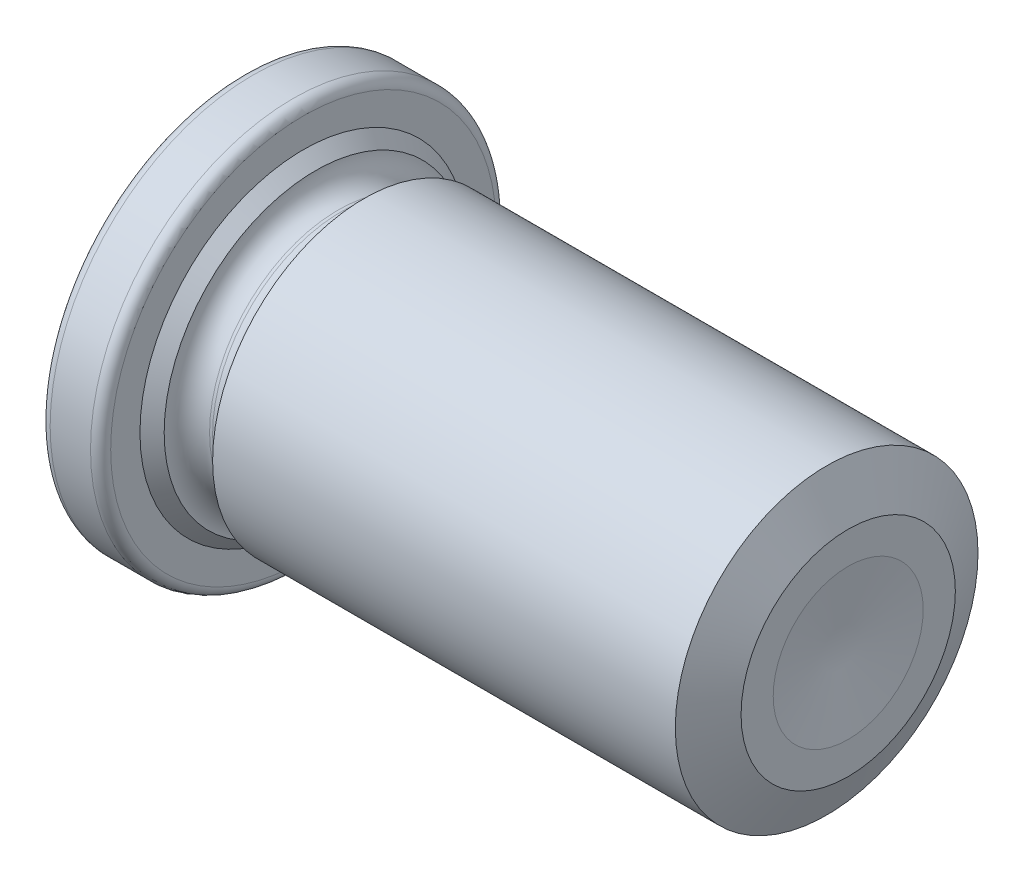
SolidWorks part; units mm, degrees
ref_plane "Front" through (0, 0, 0) normal (0, 0, 1) x (1, 0, 0)
ref_plane "Top" through (0, 0, 0) normal (0, 1, 0) x (1, 0, 0)
ref_plane "Right" through (0, 0, 0) normal (1, 0, 0) x (0, 0, -1)
sketch "Sketch1" plane through (0, 0, 0) normal (0, 0, 1) x (1, 0, 0)
  line L0 (-6.35, 0) -> (6.35, 0) construction
  line L1 (-6.35, 0) -> (-6.35, 4.2545)
  line L2 (-6.35, 4.2545) -> (-5.08, 4.2545)
  line L3 (-5.08, 4.2545) -> (-5.08, 3.429)
  line L4 (-5.08, 3.429) -> (-4.826, 3.175)
  line L5 (-4.826, 3.175) -> (-4.826, 2.6987)
  line L6 (-4.826, 2.6987) -> (-3.81, 2.6987)
  line L7 (-3.81, 2.6987) -> (-3.81, 3.175)
  line L8 (-3.81, 3.175) -> (5.8978, 3.175)
  line L9 (5.8978, 3.175) -> (6.35, 2.2479)
  line L10 (6.35, 2.2479) -> (6.35, 1.5735)
  line L11 (-6.35, 0) -> (6.1239, 0)
  line L12 (6.35, 1.5735) -> (6.1239, 0)
  line L13 (6.1239, 2.7114) -> (6.1239, 0) construction
  dimension "L" = 12.7
  dimension "D2" = 64
  dimension "D" = 4.4958
  dimension "P" = 6.35
  dimension "H" = 8.509
  dimension "D1" = 5.3975
  dimension "D3" = 1.27
  dimension "D4" = 0.254
  dimension "D6" = 1.27
  dimension "D7" = 45
  dimension "D5" = 3.1471
revolve "Revolve1" add sketch "Sketch1" angle 360 about L0
fillet "Fillet1" radius 0.2117 2 edges at (-5.08, 0, 4.2545) (-6.35, 0, 4.2545)
fillet "Fillet2" radius 0.4763 2 edges at (-3.81, 0, 2.6987) (-4.826, 0, 2.6987)
equation "\"D1@Sketch1\" = \"P@Sketch1\"*.85"
equation "\"D3@Sketch1\" = \"L@Sketch1\"/10"
equation "\"D4@Sketch1\" = \"D3@Sketch1\"/5"
equation "\"D6@Sketch1\" = \"D3@Sketch1\""
equation "\"D5@Sketch1\" = \"D@Sketch1\"*.7"
equation "\"D1@Fillet1\" = \"D3@Sketch1\"/6"
equation "\"D1@Fillet2\" = (\"P@Sketch1\"-\"D1@Sketch1\")/2"
